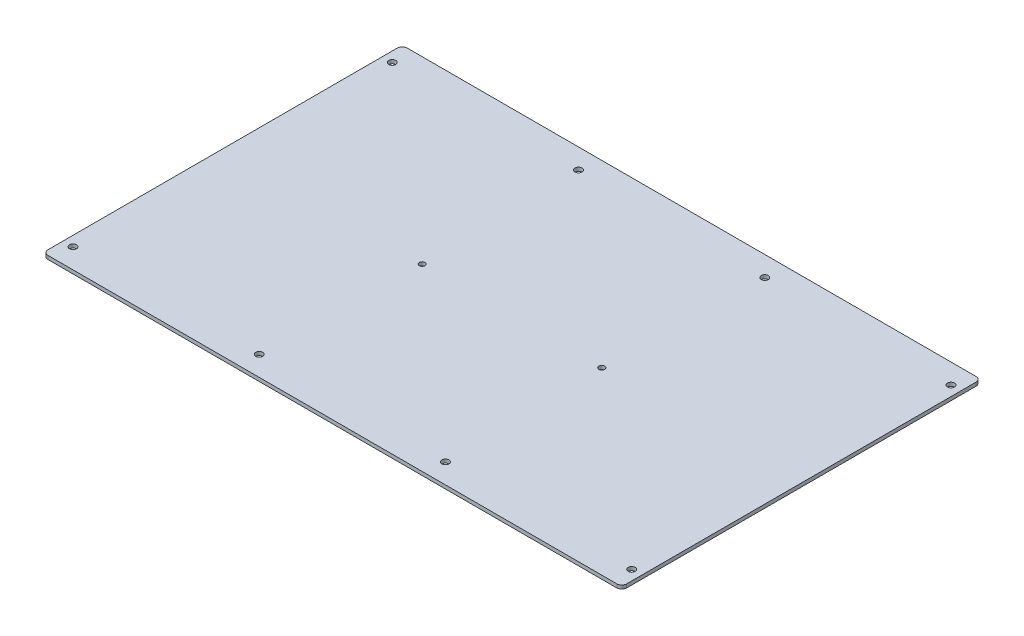
SolidWorks part; units mm, degrees
material "1060 Alloy"
ref_plane "Front" through (0, 0, 0) normal (0, 0, 1) x (1, 0, 0)
ref_plane "Top" through (0, 0, 0) normal (0, 1, 0) x (1, 0, 0)
ref_plane "Right" through (0, 0, 0) normal (1, 0, 0) x (0, 0, -1)
sketch "Sketch1" plane through (0, 0, 0) normal (0, 1, 0) x (1, 0, 0)
  line L0 (-59.2667, 0) -> (-177.8, 0) construction
  line L1 (-180.975, 114.3) -> (180.975, 114.3)
  line L2 (-184.15, 111.125) -> (-184.15, -111.125)
  line L3 (-180.975, -114.3) -> (180.975, -114.3)
  line L4 (184.15, 111.125) -> (184.15, -111.125)
  line L5 (-184.15, 114.3) -> (184.15, -114.3) construction
  line L6 (-184.15, -114.3) -> (184.15, 114.3) construction
  line L7 (-177.8, -101.6) -> (177.8, -101.6) construction
  line L8 (-177.8, -101.6) -> (-177.8, 101.6) construction
  line L9 (-177.8, 101.6) -> (177.8, 101.6) construction
  line L10 (177.8, -101.6) -> (177.8, 101.6) construction
  line L11 (-177.8, -101.6) -> (177.8, 101.6) construction
  line L12 (-177.8, 101.6) -> (177.8, -101.6) construction
  line L13 (-59.2667, -101.6) -> (59.2667, -101.6) construction
  line L14 (-59.2667, -101.6) -> (-59.2667, 101.6) construction
  line L15 (-59.2667, 101.6) -> (59.2667, 101.6) construction
  line L16 (59.2667, -101.6) -> (59.2667, 101.6) construction
  line L17 (-59.2667, -101.6) -> (59.2667, 101.6) construction
  line L18 (-59.2667, 101.6) -> (59.2667, -101.6) construction
  line L19 (59.2667, 0) -> (177.8, 0) construction
  line L20 (-59.2667, 0) -> (59.2667, 0) construction
  line L22 (136.525, -71.4375) -> (-136.525, -71.4375) construction
  line L23 (136.525, -71.4375) -> (136.525, 71.4375) construction
  line L24 (136.525, 71.4375) -> (-136.525, 71.4375) construction
  line L25 (-136.525, -71.4375) -> (-136.525, 71.4375) construction
  line L26 (136.525, -71.4375) -> (-136.525, 71.4375) construction
  line L27 (136.525, 71.4375) -> (-136.525, -71.4375) construction
  circle A0 centre (-177.8, 101.6) radius 2.2479
  circle A1 centre (-59.2667, 101.6) radius 2.2479
  circle A2 centre (59.2667, 101.6) radius 2.2479
  circle A3 centre (177.8, 101.6) radius 2.2479
  circle A4 centre (177.8, -101.6) radius 2.2479
  circle A5 centre (59.2667, -101.6) radius 2.2479
  circle A6 centre (-59.2667, -101.6) radius 2.2479
  circle A7 centre (-177.8, -101.6) radius 2.2479
  circle A8 centre (-136.525, -71.4375) radius 1.8288 construction
  circle A9 centre (-136.525, 71.4375) radius 1.8288 construction
  circle A10 centre (136.525, 71.4375) radius 1.8288 construction
  circle A11 centre (136.525, -71.4375) radius 1.8288 construction
  circle A12 centre (-57.15, 0) radius 1.8288
  circle A13 centre (57.15, 0) radius 1.8288
  arc A14 (184.15, 111.125) -> (180.975, 114.3) centre (180.975, 111.125) ccw
  arc A15 (184.15, -111.125) -> (180.975, -114.3) centre (180.975, -111.125) cw
  arc A16 (-180.975, -114.3) -> (-184.15, -111.125) centre (-180.975, -111.125) cw
  arc A17 (-180.975, 114.3) -> (-184.15, 111.125) centre (-180.975, 111.125) ccw
  point P0 (0, 0)
  point P6 (0, 0)
  point P11 (0, 0)
  point P28 (0, 0)
  dimension "D5" = 4.4958
  dimension "D8" = 3.6576
  dimension "D11" = 3.175
  dimension "D1" = 368.3
  dimension "D2" = 228.6
  dimension "D3" = 12.7
  dimension "D4" = 6.35
  dimension "D6" = 142.875
  dimension "D7" = 273.05
  dimension "D9" = 57.15
  dimension "D10" = 57.15
extrude "Boss-Extrude1" add sketch "Sketch1" along normal blind 2.286
